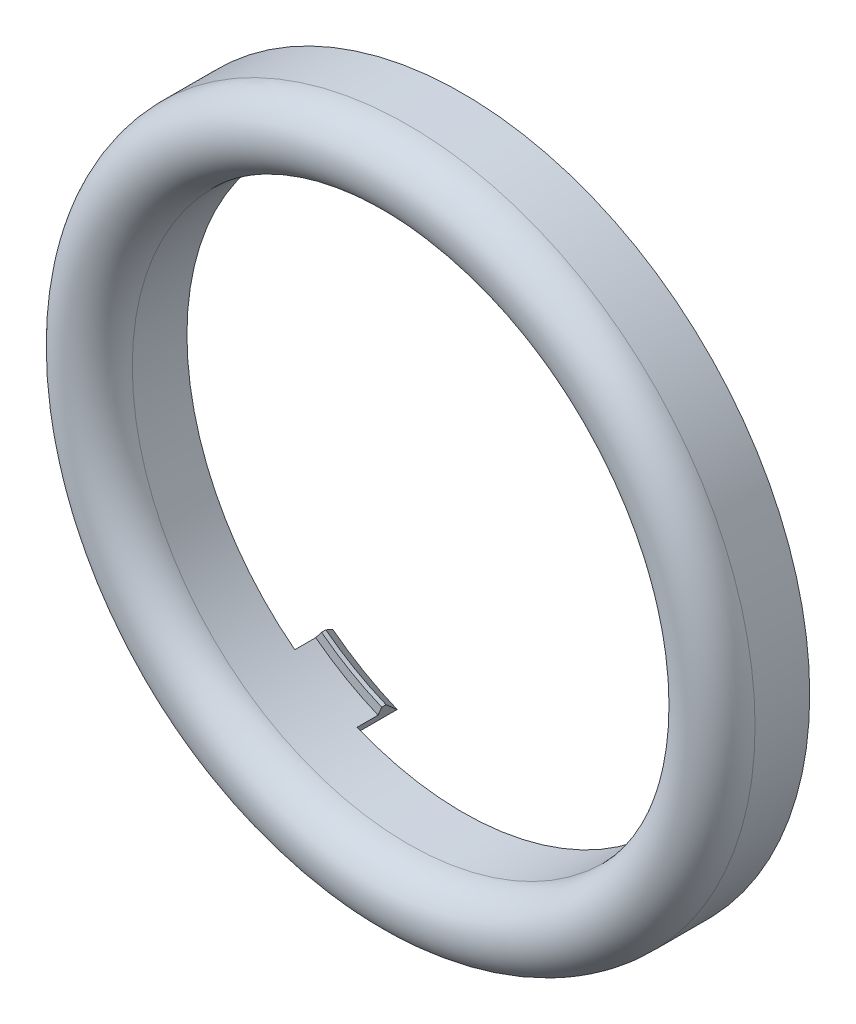
SolidWorks part; units mm, degrees
other "Diffuser" parameters "D1"=9.4806, "D2"=0.6543, "D3"=35.0559, "D4"=3.5321, "D5"=1.1612, "D6"=0.51, "D7"=2.2, "D8"=2.2, "Outside Diameter"=73, "Inside Diameter"=58
ref_plane "Top" through (0, 0, 0) normal (0, 0, 1) x (1, 0, 0)
ref_plane "Front" through (0, 0, 0) normal (0, 1, 0) x (1, 0, 0)
ref_plane "Right" through (0, 0, 0) normal (1, 0, 0) x (0, 0, -1)
sketch "Diffuser" plane through (0, 0, 0) normal (0, 1, 0) x (-1, 0, 0)
  line L0 (36.5, 0) -> (36.5, 5.75)
  line L1 (36.5, 0) -> (29, 0)
  line L2 (29, 0) -> (29, 5.75)
  line L3 (36.5, 9.5) -> (29, 9.5) construction
  line L4 (0, 0) -> (0, 10) construction
  arc A0 (36.5, 5.75) -> (29, 5.75) centre (32.75, 5.75) ccw
  dimension "D2" = 9.5
  dimension "D3" = 10
revolve "Diffuser Revolve" add sketch "Diffuser" angle 360 about L4
sketch "Tabs" plane through (36.2137, 0, -46.3233) normal (0, 1, 0) x (-1, 0, 0)
  line L0 (7.2137, 44.1233) -> (7.2137, 46.3233)
  line L1 (36.2137, 46.3233) -> (36.2137, 51.3233) construction
  line L2 (7.2137, 44.1233) -> (8.2137, 44.1233)
  line L3 (8.2137, 44.1233) -> (8.2137, 43.6733)
  line L4 (8.2137, 43.6733) -> (6.3137, 41.7733)
  line L5 (6.3137, 41.7733) -> (6.3137, 46.3233)
  line L6 (6.3137, 46.3233) -> (7.2137, 46.3233)
  dimension "D1" = 5
  dimension "D2" = 0.9
  dimension "D3" = 4.55
  dimension "D5" = 45
  dimension "D6" = 1
  dimension "D7" = 58
  dimension "D4" = 2.2
revolve "Tab Revolve" add sketch "Tabs" angle 15 mid plane about L1
pattern_circular "Tab Pattern" count 3 over 360 about axis through (0, 0, 0) along (0, 0, 1) of bodies 102
combine bodies "Ring and Tabs Combine" operation type add bodies to combine 101 104 103 102
equation "\"D7@Tabs\"=\"Inside Diameter@Diffuser\""
